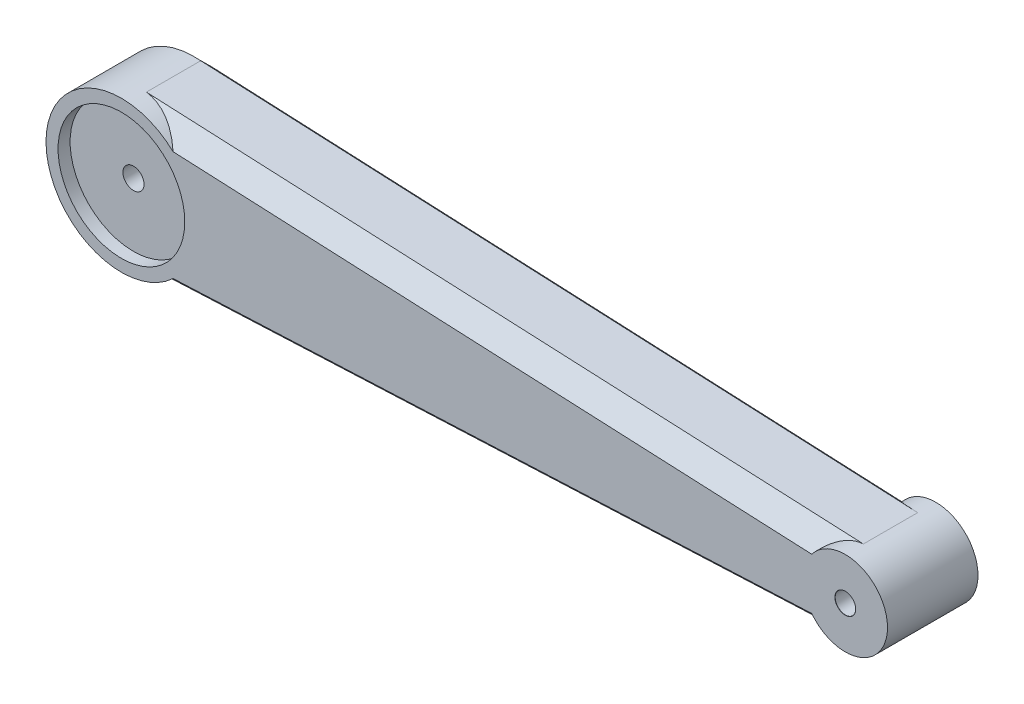
SolidWorks part; units mm, degrees
ref_plane "Front Plane" through (0, 0, 0) normal (0, 0, 1) x (1, 0, 0)
ref_plane "Top Plane" through (0, 0, 0) normal (0, 1, 0) x (1, 0, 0)
ref_plane "Right Plane" through (0, 0, 0) normal (1, 0, 0) x (0, 0, -1)
sketch "Sketch1" plane through (0, 0, 0) normal (0, 0, 1) x (1, 0, 0)
  line L1 (1.1434, 12.4476) -> (120, 7)
  line L2 (1.1434, -12.4476) -> (120, -7)
  arc A0 (1.1434, 12.4476) -> (1.1434, -12.4476) centre (0, 0) ccw
  arc A1 (120, -7) -> (120, 7) centre (120, 0) ccw
  dimension "D1" = 25
  dimension "D2" = 14
  dimension "D3" = 120
extrude "Boss-Extrude2" add sketch "Sketch1" along normal blind 15
chamfer "Chamfer2" distance 3 angle 45 2 edges at (-12.5, 0, 0) (60.5717, 9.7238, 0)
sketch "Sketch2" plane through (0, 0, 15) normal (0, 0, 1) x (1, 0, 0)
  circle A0 centre (0, 0) radius 10.5
  dimension "D1" = 21
extrude "Cut-Extrude1" cut sketch "Sketch2" against normal blind 2 contours A0
chamfer "Chamfer3" distance 3 angle 45 2 edges at (60.5717, -9.7238, 15) (60.5717, 9.7238, 15)
hole_wizard "M3 Clearance Hole1" positions "Sketch3" profile "Sketch4" hole size "M3" standard "ANSI Metric" end condition through all
sketch "Sketch3" plane through (0, 0, 15) normal (0, 0, 1) x (1, 0, 0)
  point P0 (120, 0)
sketch "Sketch4" plane through (120, 0, 15) normal (1, 0, 0) x (0, -1, 0)
  line L0 (0, 0) -> (0, 15)
  line L1 (0, 15) -> (1.7, 15)
  line L2 (1.7, 15) -> (1.7, 0.025)
  line L3 (1.7, 0.025) -> (1.725, 0)
  line L5 (1.725, 0) -> (0, 0)
  line L6 (-1.7, 0.025) -> (-1.725, 0) construction
  line L11 (0, -6.35) -> (0, 107.95) construction
  dimension "Thru Hole Dia." = 3.4
  dimension "Thru Hole Depth" = 15
  dimension "Near C'Sink Dia." = 3.45
  dimension "Near C'Sink Angle" = 90
hole_wizard "CBORE for M5 Hex Head Cap Screw1" positions "Sketch5" profile "Sketch6" counterbore size "M5" standard "ANSI Metric" end condition through all
sketch "Sketch5" plane through (0, 0, 0) normal (0, 0, -1) x (-1, 0, 0)
  point P0 (0, 0)
sketch "Sketch6" plane through (0, 0, 0) normal (1, 0, 0) x (0, 1, 0)
  line L0 (0, 0) -> (0, 15)
  line L1 (0, 15) -> (1.75, 15)
  line L3 (1.75, 15) -> (1.75, 8)
  line L4 (4, 8) -> (1.75, 8)
  line L5 (4, 8) -> (4, 2.145)
  line L6 (4, 2.145) -> (6.145, 0)
  line L7 (6.145, 0) -> (0, 0)
  line L8 (-4, 2.145) -> (-6.145, 0) construction
  line L11 (0, -6.35) -> (0, 107.95) construction
  dimension "Thru Hole Dia." = 3.5
  dimension "Thru Hole Depth" = 15
  dimension "C'Bore Dia." = 8
  dimension "C'Bore Depth" = 8
  dimension "Near C'Sink Dia." = 12.29
  dimension "Near C'Sink Angle" = 90
